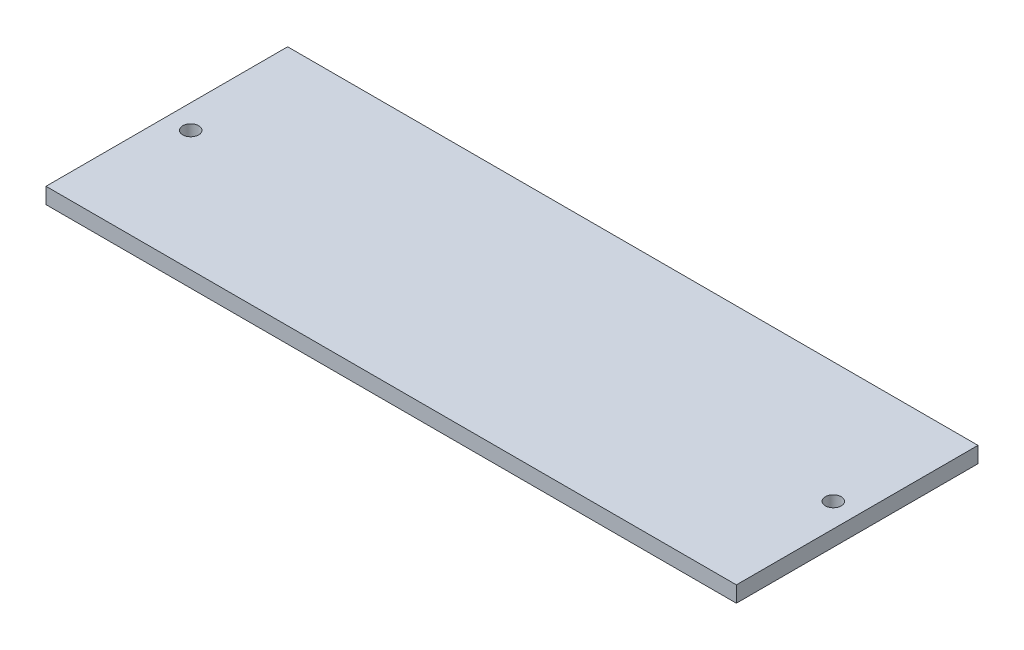
SolidWorks part; units mm, degrees
ref_plane "Front Plane" through (0, 0, 0) normal (0, 0, 1) x (1, 0, 0)
ref_plane "Top Plane" through (0, 0, 0) normal (0, 1, 0) x (1, 0, 0)
ref_plane "Right Plane" through (0, 0, 0) normal (1, 0, 0) x (0, 0, -1)
sketch "Sketch1" plane through (0, 0, 0) normal (0, 1, 0) x (1, 0, 0)
  line L0 (0, 0) -> (0, 22.75) construction
  line L1 (-65, 22.75) -> (65, 22.75)
  line L2 (-65, 22.75) -> (-65, -22.75)
  line L3 (-65, -22.75) -> (65, -22.75)
  line L4 (65, 22.75) -> (65, -22.75)
  line L5 (-65, 22.75) -> (65, -22.75) construction
  line L6 (-65, -22.75) -> (65, 22.75) construction
  line L7 (0, 0) -> (65, 0) construction
  circle A1 centre (60.5, 0) radius 1.5
  circle A2 centre (-60.5, 0) radius 1.5
  point P0 (0, 0)
  dimension "D3" = 3
  dimension "D4" = 4.5
  dimension "D5" = 0
  dimension "D1" = 45.5
  dimension "D2" = 130
extrude "Boss-Extrude1" add sketch "Sketch1" along normal blind 3
